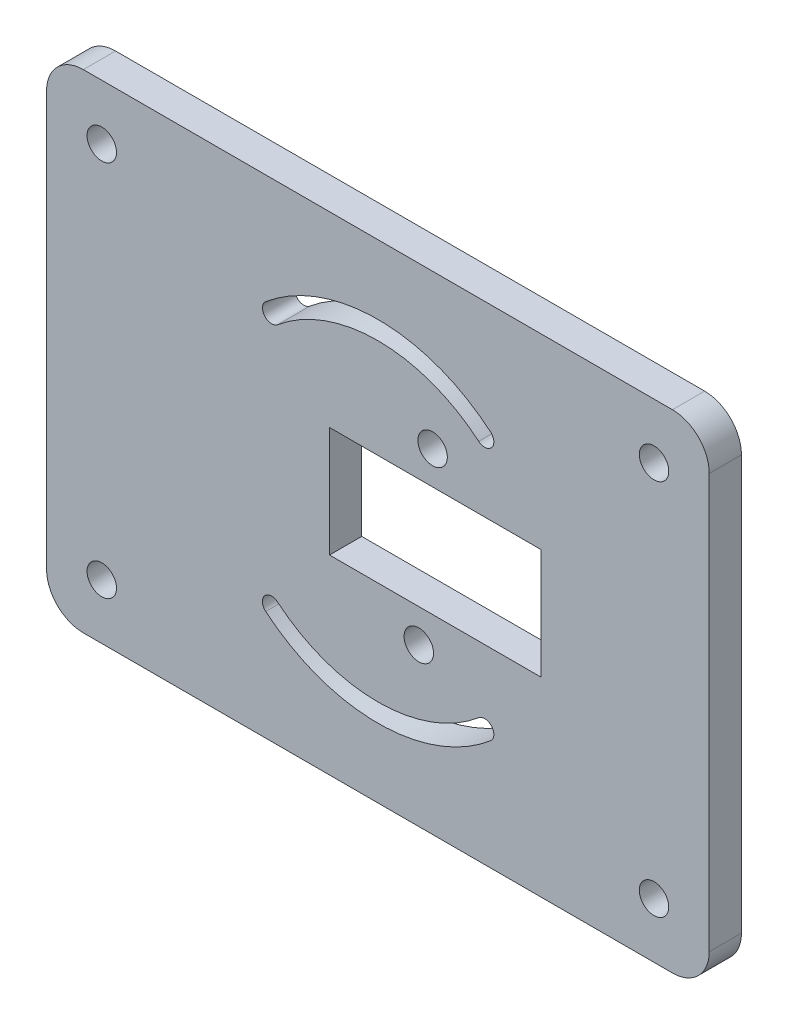
SolidWorks part; units mm, degrees
material "Balsa"
ref_plane "Front Plane" through (0, 0, 0) normal (0, 0, 1) x (1, 0, 0)
ref_plane "Top Plane" through (0, 0, 0) normal (0, 1, 0) x (1, 0, 0)
ref_plane "Right Plane" through (0, 0, 0) normal (1, 0, 0) x (0, 0, -1)
sketch "Sketch1" plane through (0, 0, 0) normal (0, 0, 1) x (1, 0, 0)
  line L5 (-0.0442, 0) -> (-0.0442, 26.5) construction
  line L6 (-32.0442, -26.5) -> (31.9558, -26.5)
  line L34 (-36.0442, -22.5) -> (-36.0442, 22.5)
  line L37 (-32.0442, 26.5) -> (31.9558, 26.5)
  line L40 (35.9558, -22.5) -> (35.9558, 22.5)
  line L43 (-5.3, 6.2) -> (17.7, 6.2)
  line L44 (-5.3, 6.2) -> (-5.3, -5.8)
  line L45 (-5.3, -5.8) -> (17.7, -5.8)
  line L46 (17.7, 6.2) -> (17.7, -5.8)
  line L47 (-0.0442, 0) -> (-0.0442, -26.5) construction
  line L48 (-0.0442, 0) -> (-36.0442, 0) construction
  line L49 (-0.0442, 0) -> (35.9558, 0) construction
  line L50 (-22.2361, -26.5) -> (22.2361, 26.5) construction
  line L51 (-22.2361, 26.5) -> (22.2361, -26.5) construction
  circle A7 centre (29.9558, -20.5) radius 1.6
  circle A8 centre (29.9558, 20.5) radius 1.6
  circle A9 centre (-30.0442, 20.5) radius 1.6
  circle A10 centre (-30.0442, -20.5) radius 1.6
  circle A11 centre (5.9, 9.8) radius 1.6
  circle A12 centre (4.4, -9.4) radius 1.6
  arc A13 (35.9558, 22.5) -> (31.9558, 26.5) centre (31.9558, 22.5) ccw
  arc A14 (31.9558, -26.5) -> (35.9558, -22.5) centre (31.9558, -22.5) ccw
  arc A15 (-32.0442, -26.5) -> (-36.0442, -22.5) centre (-32.0442, -22.5) cw
  arc A16 (-32.0442, 26.5) -> (-36.0442, 22.5) centre (-32.0442, 22.5) ccw
  arc A17 (-11.5884, -13.8105) -> (11.5519, -13.767) centre (-0.0442, 0) ccw construction
  arc A18 (-12.2298, -14.5778) -> (12.1961, -14.5318) centre (-0.0442, 0) ccw
  arc A19 (-10.9471, -13.0433) -> (10.9077, -13.0022) centre (-0.0442, 0) ccw
  arc A20 (-10.9471, -13.0433) -> (-12.2298, -14.5778) centre (-11.5884, -13.8105) ccw
  arc A21 (12.1961, -14.5318) -> (10.9077, -13.0022) centre (11.5519, -13.767) ccw
  arc A22 (-11.5884, 13.8105) -> (11.5519, 13.767) centre (-0.0442, 0) cw construction
  arc A23 (-12.2298, 14.5778) -> (12.1961, 14.5318) centre (-0.0442, 0) cw
  arc A24 (-10.9471, 13.0433) -> (10.9077, 13.0022) centre (-0.0442, 0) cw
  arc A25 (-10.9471, 13.0433) -> (-12.2298, 14.5778) centre (-11.5884, 13.8105) cw
  arc A26 (12.1961, 14.5318) -> (10.9077, 13.0022) centre (11.5519, 13.767) cw
  point P0 (0, 0)
  point P4 (-0.0103, -18)
  point P47 (-0.0103, 18)
  dimension "D6" = 6
  dimension "D11" = 12
  dimension "D1" = 3.2
  dimension "D14" = 11.8
  dimension "D18" = 4
  dimension "D24" = 18
  dimension "D2" = 6
  dimension "D3" = 6
  dimension "D4" = 6
  dimension "D5" = 6
  dimension "D7" = 6
  dimension "D8" = 6
  dimension "D9" = 6
  dimension "D10" = 23
  dimension "D12" = 5.8
  dimension "D13" = 5.3
  dimension "D15" = 3.6
  dimension "D16" = 3.6
  dimension "D17" = 13.3
  dimension "D19" = 50
  dimension "D20" = 72
  dimension "D21" = 50
  dimension "D22" = 36.0442
  dimension "D23" = 53
  dimension "D25" = 2
extrude "Boss-Extrude1" add sketch "Sketch1" along normal blind 3.5
